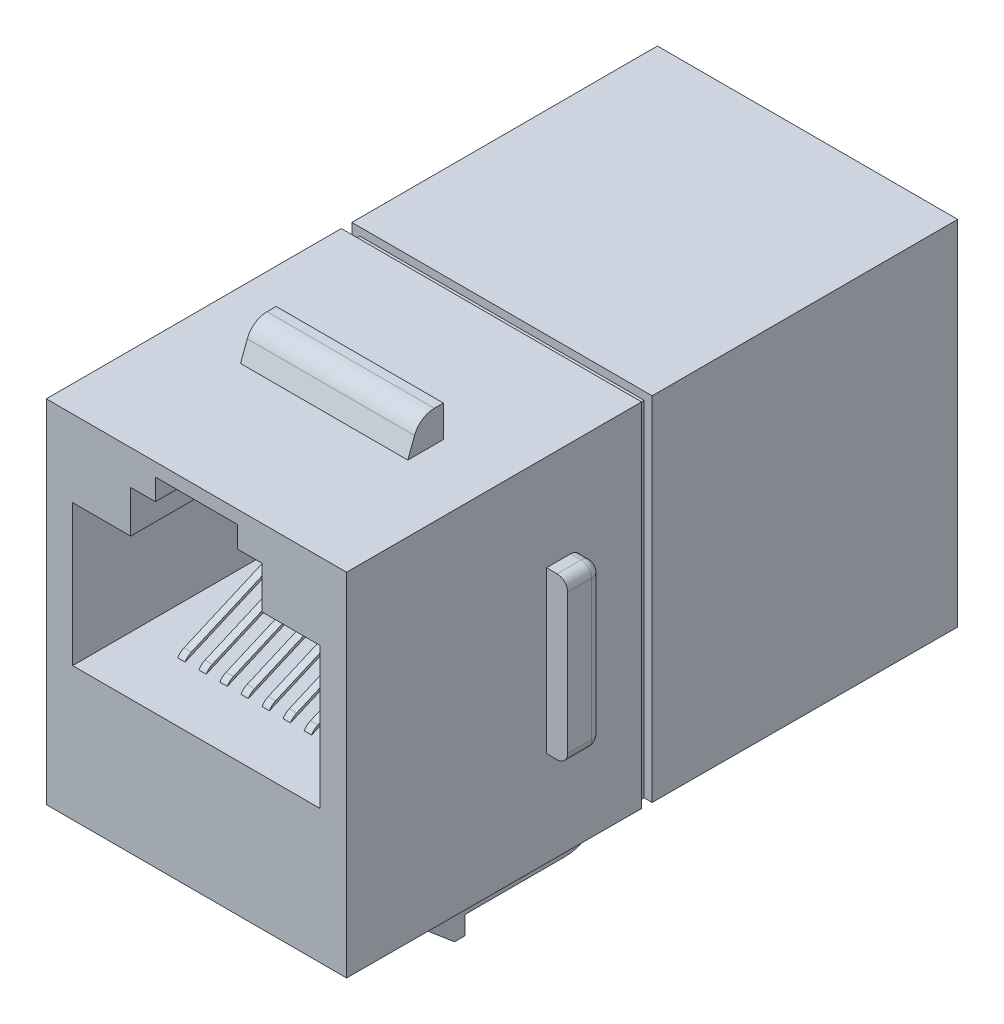
SolidWorks part; units mm, degrees
ref_plane "Front Plane" through (0, 0, 0) normal (0, 0, 1) x (1, 0, 0)
ref_plane "Top Plane" through (0, 0, 0) normal (0, 1, 0) x (1, 0, 0)
ref_plane "Right Plane" through (0, 0, 0) normal (1, 0, 0) x (0, 0, -1)
sketch "Sketch1" plane through (0, 0, 0) normal (1, 0, 0) x (0, 0, -1)
  line L0 (-14.732, 0) -> (14.732, 0) construction
  line L1 (0, -10.8585) -> (0, 10.8585) construction
  line L2 (-6.858, -9.9695) -> (-2.0828, -9.9695) construction
  line L3 (-14.732, -7.6073) -> (0.2032, -7.6835) construction
  line L5 (0.2032, -7.6835) -> (14.732, -7.6835) construction
  line L6 (14.732, -7.6835) -> (14.732, 9.3345) construction
  line L7 (14.732, 9.3345) -> (-5.0292, 9.3345) construction
  line L8 (-6.858, 10.8585) -> (-8.001, 10.8585) construction
  line L10 (14.732, -7.6835) -> (14.732, 9.3345) construction
  line L11 (14.732, 0.8255) -> (-14.732, 0.8213) construction
  line L12 (-5.0927, -3.0572) -> (-3.937, -3.0572) construction
  line L14 (-5.0927, -3.0572) -> (-5.0927, 4.7025) construction
  line L15 (14.732, 9.3345) -> (14.732, -7.6835) construction
  line L16 (-5.0927, 4.7025) -> (-3.937, 4.7025) construction
  line L26 (-0.508, -7.6799) -> (-0.508, 9.3345) construction
  line L27 (-3.429, -2.5492) -> (-3.429, 4.1945) construction
  line L28 (-8.001, 10.8585) -> (-8.5852, 9.3035) construction
  arc A2 (-3.937, 4.7025) -> (-3.429, 4.1945) centre (-3.937, 4.1945) cw construction
  arc A3 (-3.937, -3.0572) -> (-3.429, -2.5492) centre (-3.937, -2.5492) ccw construction
  point P4 (0, 0)
  point P8 (0, 0)
  point P23 (-5.0927, 0.8226)
  point P32 (-3.429, -3.0572)
  line B0 (-14.732, -7.6073) -> (-14.732, 9.2498) construction
  line B1 (-14.732, 9.2498) -> (-5.0292, 9.3345) construction
  line B2 (-5.0292, 9.3345) -> (-5.0292, -7.6073) construction
  line B3 (-9.5662, 9.2949) -> (-6.858, 10.8585) construction
  line B4 (-6.858, 10.8585) -> (-6.858, 9.3185) construction
  line B5 (-6.858, -9.9695) -> (-6.858, -10.8585) construction
  line B6 (-6.858, -10.8585) -> (-7.2771, -10.8585) construction
  line B7 (-8.9317, -9.5312) -> (-7.4416, -10.798) construction
  line B8 (-8.7757, -8.9408) -> (-2.7051, -8.7376) construction
  line B9 (-9.0212, -9.1947) -> (-9.0212, -9.3377) construction
  arc B10 (0.2032, -7.6835) -> (-2.0828, -9.9695) centre (-2.0828, -7.6835) cw construction
  arc B11 (-8.7757, -8.9408) -> (-9.0212, -9.1947) centre (-8.7672, -9.1947) ccw construction
  arc B12 (-9.0212, -9.3377) -> (-8.9317, -9.5312) centre (-8.7672, -9.3377) ccw construction
  arc B13 (-7.2771, -10.8585) -> (-7.4416, -10.798) centre (-7.2771, -10.6045) cw construction
  arc B14 (-2.7051, -8.7376) -> (-1.7225, -7.7216) centre (-2.7391, -7.7216) ccw construction
  dimension "D6" = 0.508
  dimension "D1" = 1.143
  dimension "Length" = 29.464
  dimension "Height" = 21.717
  dimension "D2" = 1.7272
  dimension "D3" = 2.921
  dimension "Groove Width" = 0.508
  dimension "Tab length" = 1.6637
  dimension "Tab Height" = 7.7597
sketch_block_instance "RJ45 Female-1"
sketch_block "RJ45 Female" parameters "D6"=0.254, "D1"=60, "D2"=10.6553, "D3"=90.5, "D4"=0.762, "D5"=0.889, "D7"=1.0287, "D8"=0.4191, "D9"=1.9558, "D10"=1.9177, "D11"=4.1529, "D12"=1.2319, "D13"=0.762
sketch "Sketch2" plane through (0, 0, 0) normal (0, 0, 1) x (1, 0, 0)
  line L1 (-8.2233, 10.8585) -> (8.2233, 10.8585) construction
  line L2 (-8.2233, 10.8585) -> (-8.2233, -10.8585) construction
  line L3 (-8.2233, -10.8585) -> (8.2233, -10.8585) construction
  line L4 (8.2233, 10.8585) -> (8.2233, -10.8585) construction
  line L5 (-7.239, 9.2498) -> (7.239, 9.2498) construction
  line L6 (-7.239, 9.2498) -> (-7.239, -7.6073) construction
  line L7 (-7.239, -7.6073) -> (7.239, -7.6073) construction
  line L8 (7.239, 9.2498) -> (7.239, -7.6073) construction
  point P4 (0, 9.2498)
  point P6 (0, 9.2498)
  point P10 (0, -7.6073)
  line B0 (-8.6233, 10.8585) -> (8.6233, 10.8585) construction
  line B1 (-5.969, -1.1684) -> (5.969, -1.1684) construction
  line B2 (5.969, -1.1684) -> (5.969, 5.6388) construction
  line B3 (-5.969, 5.6388) -> (5.969, 5.6388) construction
  line B4 (-5.969, 5.6388) -> (-5.969, -1.1684) construction
  line B5 (-3.1687, 5.6388) -> (-3.1687, 7.6708) construction
  line B6 (3.1686, 7.6708) -> (3.1686, 5.6388) construction
  line B7 (-5.715, 9.5885) -> (-4.2863, 9.5885) construction
  line B8 (-4.0323, 9.8425) -> (-4.0323, 10.6045) construction
  line B9 (4.0322, 10.6045) -> (4.0322, 9.8425) construction
  line B10 (4.2862, 9.5885) -> (5.715, 9.5885) construction
  line B11 (-5.969, -0.4064) -> (-3.8354, -0.4064) construction
  line B12 (-3.8354, -0.4064) -> (-3.8354, 2.1336) construction
  line B13 (-3.2766, 2.1336) -> (-3.2766, -0.4064) construction
  line B14 (-3.2766, -0.4064) -> (-2.8194, -0.4064) construction
  line B15 (-2.8194, -0.4064) -> (-2.8194, 2.1336) construction
  line B16 (-2.8194, 2.1336) -> (-2.2606, 2.1336) construction
  line B17 (-2.2606, 2.1336) -> (-2.2606, -0.4064) construction
  line B18 (-2.2606, -0.4064) -> (-1.8034, -0.4064) construction
  line B19 (-1.8034, -0.4064) -> (-1.8034, 2.1336) construction
  line B20 (-1.8034, 2.1336) -> (-1.2446, 2.1336) construction
  line B21 (-1.2446, 2.1336) -> (-1.2446, -0.4064) construction
  line B22 (-1.2446, -0.4064) -> (-0.7874, -0.4064) construction
  line B23 (-0.7874, -0.4064) -> (-0.7874, 2.1336) construction
  line B24 (-0.7874, 2.1336) -> (-0.2286, 2.1336) construction
  line B25 (-0.2286, 2.1336) -> (-0.2286, -0.4064) construction
  line B26 (-0.2286, -0.4064) -> (0.2286, -0.4064) construction
  line B27 (0.2286, -0.4064) -> (0.2286, 2.1336) construction
  line B28 (0.2286, 2.1336) -> (0.7874, 2.1336) construction
  line B29 (0.7874, 2.1336) -> (0.7874, -0.4064) construction
  line B30 (0.7874, -0.4064) -> (1.2446, -0.4064) construction
  line B31 (1.2446, -0.4064) -> (1.2446, 2.1336) construction
  line B32 (1.2446, 2.1336) -> (1.8034, 2.1336) construction
  line B33 (1.8034, 2.1336) -> (1.8034, -0.4064) construction
  line B34 (1.8034, -0.4064) -> (2.2606, -0.4064) construction
  line B35 (2.2606, -0.4064) -> (2.2606, 2.1336) construction
  line B36 (2.8194, 2.1336) -> (2.8194, -0.4064) construction
  line B37 (2.8194, -0.4064) -> (3.2766, -0.4064) construction
  line B38 (3.2766, -0.4064) -> (3.2766, 2.1336) construction
  line B39 (3.2766, 2.1336) -> (3.8354, 2.1336) construction
  line B40 (3.8354, 2.1336) -> (3.8354, -0.4064) construction
  line B41 (3.8354, -0.4064) -> (5.969, -0.4064) construction
  line B42 (-3.7592, 2.1336) -> (-3.7592, -1.1684) construction
  line B43 (-3.4036, -1.1684) -> (-3.4036, 2.1336) construction
  dimension "Width" = 16.4465
  dimension "Body Width" = 14.478
sketch_block_instance "RJ45 Female Front-1"
sketch_block "RJ45 Female Front" parameters "D1"=17.2466, "D2"=11.938, "D3"=6.8072, "D4"=5.2197, "D5"=8.0645, "D6"=0.762, "D7"=2.1336, "D8"=0.5588, "D9"=2.54, "D10"=0.4572, "D11"=0.0762, "D12"=0.127
sketch "Sketch3" plane through (0, 0, 0) normal (1, 0, 0) x (0, 0, -1)
  line L0 (-14.732, 9.3345) -> (14.732, 9.3345)
  line L1 (14.732, 9.3345) -> (14.732, -7.6835)
  line L2 (14.732, -7.6835) -> (-14.732, -7.6073)
  line L4 (-14.732, -7.6073) -> (-14.732, 9.3345)
  line L9 (14.732, 9.3345) -> (-5.0292, 9.3345) construction
  line L10 (14.732, -7.6835) -> (14.732, 9.3345) construction
extrude "Boss-Extrude1" add sketch "Sketch3" against normal up to vertex (7.239 mm away) and the other way up to vertex (7.239 mm away) up to point (-7.239, 9.2498, 0) other way up to point (7.239, 9.2498, 0)
sketch "Sketch4" plane through (0, 0, 0) normal (1, 0, 0) x (0, 0, -1)
  line L0 (-8.001, 10.8585) -> (-8.5852, 9.3035) construction
  line L1 (-6.858, 10.8585) -> (-8.001, 10.8585) construction
  line L6 (-8.2485, 10.1998) -> (-8.5852, 9.3035)
  line L10 (-6.858, 10.8585) -> (-6.858, 9.3185)
  line L11 (-6.858, 9.3185) -> (-8.5852, 9.3035)
  line L12 (-6.858, 10.8585) -> (-7.2974, 10.8585)
  arc A0 (-8.2485, 10.1998) -> (-7.2974, 10.8585) centre (-7.2974, 9.8425) cw
  dimension "D1" = 1.016
extrude "Boss-Extrude2" add sketch "Sketch4" against normal up to vertex (4.0323 mm away) and the other way up to vertex (4.0323 mm away) up to point (-4.0323, 10.6045, 0) other way up to point (4.0322, 10.6045, 0)
sketch "Sketch5" plane through (0, 0, 0) normal (1, 0, 0) x (0, 0, -1)
  line L0 (-6.858, -9.9695) -> (-6.858, -10.8585) construction
  line L1 (-6.858, -10.8585) -> (-7.2771, -10.8585) construction
  line L2 (-8.9317, -9.5312) -> (-7.4416, -10.798) construction
  line L3 (-9.0212, -9.1947) -> (-9.0212, -9.3377) construction
  line L4 (-8.7757, -8.9408) -> (-2.7051, -8.7376) construction
  line L5 (-6.858, -9.9695) -> (-2.0828, -9.9695) construction
  line L6 (-6.858, -9.9695) -> (-6.858, -10.8585)
  line L7 (-6.858, -10.8585) -> (-7.2771, -10.8585)
  line L8 (-8.9317, -9.5312) -> (-7.4416, -10.798)
  line L9 (-9.0212, -9.1947) -> (-9.0212, -9.3377)
  line L10 (-8.7757, -8.9408) -> (-2.7051, -8.7376)
  line L11 (-6.858, -9.9695) -> (-2.0828, -9.9695)
  line L12 (0.2032, -7.6835) -> (0.2032, -7.6459)
  line L13 (-14.732, -7.6073) -> (14.732, -7.6835) construction
  line L14 (0.2032, -7.6459) -> (-1.7225, -7.6409)
  line L15 (-1.7225, -7.6409) -> (-1.7225, -7.7216)
  arc A0 (-7.4416, -10.798) -> (-7.2771, -10.8585) centre (-7.2771, -10.6045) ccw construction
  arc A1 (-9.0212, -9.3377) -> (-8.9317, -9.5312) centre (-8.7672, -9.3377) ccw construction
  arc A2 (-8.7757, -8.9408) -> (-9.0212, -9.1947) centre (-8.7672, -9.1947) ccw construction
  arc A3 (-2.0828, -9.9695) -> (0.2032, -7.6835) centre (-2.0828, -7.6835) ccw construction
  arc A4 (-2.7051, -8.7376) -> (-1.7225, -7.7216) centre (-2.7391, -7.7216) ccw construction
  arc A5 (-7.4416, -10.798) -> (-7.2771, -10.8585) centre (-7.2771, -10.6045) ccw
  arc A6 (-9.0212, -9.3377) -> (-8.9317, -9.5312) centre (-8.7672, -9.3377) ccw
  arc A7 (-8.7757, -8.9408) -> (-9.0212, -9.1947) centre (-8.7672, -9.1947) ccw
  arc A8 (-2.0828, -9.9695) -> (0.2032, -7.6835) centre (-2.0828, -7.6835) ccw
  arc A9 (-2.7051, -8.7376) -> (-1.7225, -7.7216) centre (-2.7391, -7.7216) ccw
extrude "Boss-Extrude3" add sketch "Sketch5" along normal mid plane 10.16
sketch "Sketch6" plane through (0, 0, 14.732) normal (0, 0, 1) x (1, 0, 0)
  line L0 (-5.969, 5.6388) -> (-5.969, -1.1684) construction
  line L1 (-5.969, -1.1684) -> (5.969, -1.1684) construction
  line L2 (5.969, -1.1684) -> (5.969, 5.6388) construction
  line L3 (3.1686, 7.6708) -> (3.1686, 5.6388) construction
  line L4 (-5.969, 5.6388) -> (5.969, 5.6388) construction
  line L5 (-3.1687, 5.6388) -> (-3.1687, 7.6708) construction
  line L6 (-5.969, 5.6388) -> (-5.969, -1.1684)
  line L7 (-5.969, -1.1684) -> (5.969, -1.1684)
  line L8 (5.969, -1.1684) -> (5.969, 5.6388)
  line L9 (3.1686, 7.6708) -> (3.1686, 5.6388)
  line L10 (-5.969, 5.6388) -> (-3.1687, 5.6388)
  line L11 (-3.1687, 5.6388) -> (-3.1687, 7.6708)
  line L12 (-3.1687, 7.6708) -> (3.1686, 7.6708)
  line L13 (3.1686, 5.6388) -> (5.969, 5.6388)
extrude "Cut-Extrude1" cut sketch "Sketch6" against normal blind 9.8933
sketch "Sketch18" plane through (0, 0, 0) normal (1, 0, 0) x (0, 0, -1)
  line L0 (-12.192, -1.1684) -> (-2.032, 3.2343)
  line L1 (-12.192, -1.1684) -> (-11.8726, -1.1684)
  line L2 (-11.8726, -1.1684) -> (-2.032, 3.0959)
  line L3 (-2.032, 3.0959) -> (-2.032, 3.2343)
  line L4 (-14.732, 5.6388) -> (-14.732, -1.1684)
  line L5 (-14.732, -1.1684) -> (-4.8387, -1.1684)
  line L6 (-4.8387, -1.1684) -> (-4.8387, 5.6388)
  line L7 (-4.8387, 5.6388) -> (-14.732, 5.6388)
  line L8 (-14.732, 5.6388) -> (-14.732, -1.1684) construction
  line L9 (-14.732, -1.1684) -> (-2.032, -1.1684) construction
  line L10 (-2.032, -1.1684) -> (-2.032, 5.6388) construction
  line L11 (-2.032, 5.6388) -> (-14.732, 5.6388) construction
  line L12 (-4.572, 5.6388) -> (-4.572, -1.1684) construction
  point P10 (-4.572, 2.1336)
  dimension "D2" = 2.54
  dimension "D3" = 0.127
  dimension "D4" = 10.16
  dimension "D5" = 2.54
  dimension "D1" = 0
extrude "Boss-Extrude6" add sketch "Sketch18" along normal up to vertex (3.7592 mm away) from vertex at -3.4036 separate body
fillet "Fillet5" radius 0.635 1 edges at (-3.5814, -1.1684, 12.192)
pattern_linear "LPattern1" count 8 spacing 1.016 along (1, 0, 0) of "Boss-Extrude6"
sketch "Sketch22" plane through (0, 0, 0) normal (0, 0, 1) x (1, 0, 0)
  line L0 (-3.2766, -0.4064) -> (-2.8194, -0.4064) construction
  line L1 (-2.2606, -0.4064) -> (-1.8034, -0.4064) construction
  line L2 (-1.2446, -0.4064) -> (-0.7874, -0.4064) construction
  line L3 (-0.2286, -0.4064) -> (0.2286, -0.4064) construction
  line L4 (0.7874, -0.4064) -> (1.2446, -0.4064) construction
  line L5 (1.8034, -0.4064) -> (2.2606, -0.4064) construction
  line L6 (2.8194, -0.4064) -> (3.2766, -0.4064) construction
  line L7 (3.8354, -0.4064) -> (5.969, -0.4064) construction
  line L8 (3.8354, 2.1336) -> (3.8354, -0.4064) construction
  line L9 (3.2766, 2.1336) -> (3.8354, 2.1336) construction
  line L10 (3.2766, -0.4064) -> (3.2766, 2.1336) construction
  line L11 (2.8194, 2.1336) -> (2.8194, -0.4064) construction
  line L12 (2.2606, -0.4064) -> (2.2606, 2.1336) construction
  line L13 (1.8034, 2.1336) -> (1.8034, -0.4064) construction
  line L14 (1.2446, 2.1336) -> (1.8034, 2.1336) construction
  line L15 (1.2446, -0.4064) -> (1.2446, 2.1336) construction
  line L16 (0.7874, 2.1336) -> (0.7874, -0.4064) construction
  line L17 (0.2286, 2.1336) -> (0.7874, 2.1336) construction
  line L18 (0.2286, -0.4064) -> (0.2286, 2.1336) construction
  line L19 (-0.2286, 2.1336) -> (-0.2286, -0.4064) construction
  line L20 (-0.7874, 2.1336) -> (-0.2286, 2.1336) construction
  line L21 (-0.7874, -0.4064) -> (-0.7874, 2.1336) construction
  line L22 (-1.2446, 2.1336) -> (-1.2446, -0.4064) construction
  line L23 (-1.8034, 2.1336) -> (-1.2446, 2.1336) construction
  line L24 (-1.8034, -0.4064) -> (-1.8034, 2.1336) construction
  line L25 (-2.2606, 2.1336) -> (-2.2606, -0.4064) construction
  line L26 (-2.8194, 2.1336) -> (-2.2606, 2.1336) construction
  line L27 (-2.8194, -0.4064) -> (-2.8194, 2.1336) construction
  line L28 (-3.2766, 2.1336) -> (-3.2766, -0.4064) construction
  line L29 (-3.8354, -0.4064) -> (-3.8354, 2.1336) construction
  line L30 (-5.969, -0.4064) -> (-3.8354, -0.4064) construction
  line L31 (-3.2766, -0.4064) -> (-2.8194, -0.4064)
  line L32 (-2.2606, -0.4064) -> (-1.8034, -0.4064)
  line L33 (-1.2446, -0.4064) -> (-0.7874, -0.4064)
  line L34 (-0.2286, -0.4064) -> (0.2286, -0.4064)
  line L35 (0.7874, -0.4064) -> (1.2446, -0.4064)
  line L36 (1.8034, -0.4064) -> (2.2606, -0.4064)
  line L37 (2.8194, -0.4064) -> (3.2766, -0.4064)
  line L38 (3.8354, -0.4064) -> (5.969, -0.4064)
  line L39 (3.8354, 2.1336) -> (3.8354, -0.4064)
  line L40 (3.2766, 2.1336) -> (3.8354, 2.1336)
  line L41 (3.2766, -0.4064) -> (3.2766, 2.1336)
  line L42 (2.8194, 2.1336) -> (2.8194, -0.4064)
  line L43 (2.2606, -0.4064) -> (2.2606, 2.1336)
  line L44 (1.8034, 2.1336) -> (1.8034, -0.4064)
  line L45 (1.2446, 2.1336) -> (1.8034, 2.1336)
  line L46 (1.2446, -0.4064) -> (1.2446, 2.1336)
  line L47 (0.7874, 2.1336) -> (0.7874, -0.4064)
  line L48 (0.2286, 2.1336) -> (0.7874, 2.1336)
  line L49 (0.2286, -0.4064) -> (0.2286, 2.1336)
  line L50 (-0.2286, 2.1336) -> (-0.2286, -0.4064)
  line L51 (-0.7874, 2.1336) -> (-0.2286, 2.1336)
  line L52 (-0.7874, -0.4064) -> (-0.7874, 2.1336)
  line L53 (-1.2446, 2.1336) -> (-1.2446, -0.4064)
  line L54 (-1.8034, 2.1336) -> (-1.2446, 2.1336)
  line L55 (-1.8034, -0.4064) -> (-1.8034, 2.1336)
  line L56 (-2.2606, 2.1336) -> (-2.2606, -0.4064)
  line L57 (-2.8194, 2.1336) -> (-2.2606, 2.1336)
  line L58 (-2.8194, -0.4064) -> (-2.8194, 2.1336)
  line L59 (-3.2766, 2.1336) -> (-3.2766, -0.4064)
  line L60 (-3.8354, -0.4064) -> (-3.8354, 2.1336)
  line L61 (-5.969, -0.4064) -> (-3.8354, -0.4064)
  line L62 (-5.969, -1.1684) -> (5.969, -1.1684) construction
  line L63 (-5.969, 5.6388) -> (-5.969, -1.1684) construction
  line L64 (-5.969, -1.1684) -> (5.969, -1.1684)
  line L65 (-5.969, -0.4064) -> (-5.969, -1.1684)
  line L66 (-3.8354, 2.1336) -> (-3.2766, 2.1336)
  line L67 (2.2606, 2.1336) -> (2.8194, 2.1336)
  line L68 (5.969, -0.4064) -> (5.969, -1.1684)
extrude "Cut-Extrude4" cut sketch "Sketch22" against normal through all both and the other way through all
sketch "Sketch19" plane through (0, 0, 0) normal (0, 0, 1) x (1, 0, 0)
  line L0 (7.239, 9.2498) -> (7.239, -7.6073) construction
  line L1 (7.239, 9.3345) -> (7.239, -7.6073)
  line L2 (-7.239, 9.2498) -> (-7.239, -7.6073) construction
  line L4 (-7.239, 9.3345) -> (-7.239, -7.6073)
  line L6 (6.858, 8.9535) -> (6.858, -7.6073)
  line L7 (-6.858, 8.9535) -> (6.858, 8.9535)
  line L8 (-6.858, 8.9535) -> (-6.858, -7.6073)
  line L11 (-7.239, 9.3345) -> (7.239, 9.3345) construction
  line L12 (-7.239, 9.3345) -> (7.239, 9.3345) construction
  line L13 (-7.239, 9.3345) -> (7.239, 9.3345)
  line L16 (-7.239, -7.6073) -> (-7.239, -7.9883)
  line L17 (-7.239, -7.9883) -> (-6.858, -7.9883)
  line L18 (-6.858, -7.6073) -> (-6.858, -7.9883)
  line L20 (6.858, -7.6073) -> (6.858, -7.9883)
  line L21 (6.858, -7.9883) -> (7.239, -7.9883)
  line L22 (7.239, -7.6073) -> (7.239, -7.9883)
  dimension "D1" = 0.381
extrude "Cut-Extrude2" cut sketch "Sketch19" along normal up to vertex (0.508 mm away) up to point (0, 9.3345, 0.508)
sketch "Sketch20" plane through (7.239, 0, 0) normal (1, 0, 0) x (0, 0, -1)
  line L0 (-5.0927, -3.0572) -> (-3.937, -3.0572) construction
  line L1 (-3.429, -2.5492) -> (-3.429, 4.1945) construction
  line L2 (-5.0927, 4.7025) -> (-3.937, 4.7025) construction
  line L3 (-5.0927, -3.0572) -> (-5.0927, 4.7025) construction
  line L4 (-5.0927, -3.0572) -> (-3.937, -3.0572)
  line L5 (-3.429, -2.5492) -> (-3.429, 4.1945)
  line L6 (-5.0927, 4.7025) -> (-3.937, 4.7025)
  line L7 (-5.0927, -3.0572) -> (-5.0927, 4.7025)
  arc A0 (-3.937, -3.0572) -> (-3.429, -2.5492) centre (-3.937, -2.5492) ccw construction
  arc A1 (-3.429, 4.1945) -> (-3.937, 4.7025) centre (-3.937, 4.1945) ccw construction
  arc A2 (-3.937, -3.0572) -> (-3.429, -2.5492) centre (-3.937, -2.5492) ccw
  arc A3 (-3.429, 4.1945) -> (-3.937, 4.7025) centre (-3.937, 4.1945) ccw
extrude "Boss-Extrude7" add sketch "Sketch20" along normal blind 1.016
fillet "Fillet4" radius 0.508 5 edges at (8.255, -3.0572, 4.5149) (8.255, -2.9084, 3.5778) (8.255, 0.8226, 3.429) (8.255, 4.5537, 3.5778) (8.255, 4.7025, 4.5149)
mirror "Mirror1" about plane through (0, 0, 0) normal (1, 0, 0) of "Fillet4", "Boss-Extrude7"
mirror "Mirror2" about plane through (0, 0, 0) normal (0, 0, 1) of "Cut-Extrude1"
mirror "Mirror3" about plane through (0, 0, 0) normal (0, 0, 1) of bodies 121 120 119 118 117 122 123 124
sketch "Sketch21" plane through (0, 0, 0) normal (0, 0, 1) x (1, 0, 0)
  line L0 (-7.239, 9.3345) -> (7.239, 9.3345) construction
  line L1 (-3.1687, 5.6388) -> (3.1686, 5.6388)
  line L2 (-3.1687, 5.6388) -> (-3.1687, 7.6708)
  line L3 (-3.1687, 7.6708) -> (-1.9812, 7.6708)
  line L4 (3.1686, 5.6388) -> (3.1686, 7.6708)
  line L6 (-1.9812, 7.6708) -> (-1.9812, 8.6995)
  line L7 (-1.9812, 8.6995) -> (1.9812, 8.6995)
  line L8 (1.9812, 7.6708) -> (1.9812, 8.6995)
  line L9 (0, -7.6835) -> (0, 9.3345) construction
  line L10 (1.9812, 7.6708) -> (3.1686, 7.6708)
  point P12 (0, 8.6995)
  dimension "D1" = 0.635
  dimension "D2" = 3.9624
extrude "Cut-Extrude3" cut sketch "Sketch21" against normal through all both and the other way through all
fillet "Fillet3" [suppressed] radius 0.2
